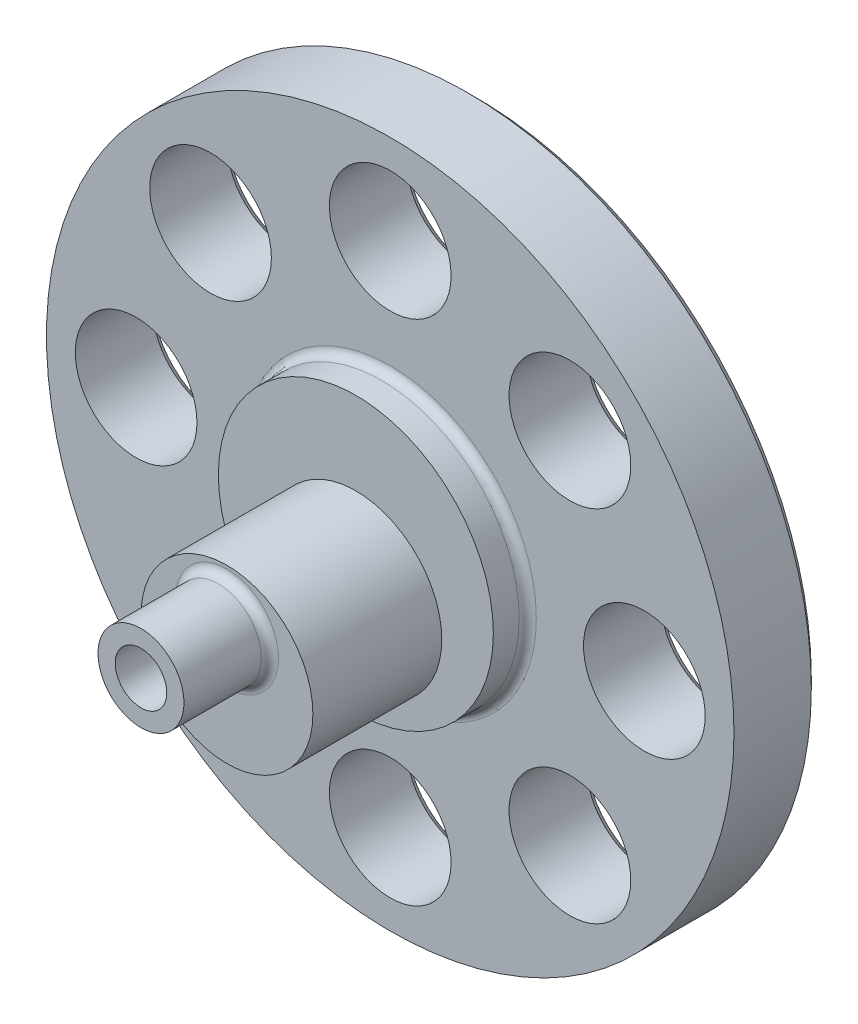
SolidWorks part; units mm, degrees
material "ABS PC"
ref_plane "Front Plane" through (0, 0, 0) normal (0, 0, 1) x (1, 0, 0)
ref_plane "Top Plane" through (0, 0, 0) normal (0, 1, 0) x (1, 0, 0)
ref_plane "Right Plane" through (0, 0, 0) normal (1, 0, 0) x (0, 0, -1)
sketch "Sketch1" plane through (0, 0, 0) normal (0, 0, 1) x (1, 0, 0)
  circle A2 centre (0, 0) radius 20
  circle A10 centre (-14.784, 0) radius 3.54
  circle A11 centre (-10.4538, -10.4538) radius 3.54
  circle A12 centre (0, -14.784) radius 3.54
  circle A13 centre (10.4538, -10.4538) radius 3.54
  circle A14 centre (14.784, 0) radius 3.54
  circle A15 centre (10.4538, 10.4538) radius 3.54
  circle A16 centre (0, 14.784) radius 3.54
  circle A17 centre (-10.4538, 10.4538) radius 3.54
  dimension "D1" = 7.08
  dimension "D2" = 40
extrude "Boss-Extrude1" add sketch "Sketch1" along normal blind 5
sketch "Sketch2" plane through (0, 0, 5) normal (0, 0, 1) x (1, 0, 0)
  circle A0 centre (0, 0) radius 8
  dimension "D1" = 16
extrude "Boss-Extrude2" add sketch "Sketch2" along normal blind 2
sketch "Sketch3" plane through (0, 0, 0) normal (0, 0, -1) x (-1, 0, 0)
  circle A0 centre (0, 0) radius 6.5
  dimension "D1" = 13
extrude "Cut-Extrude1" cut sketch "Sketch3" against normal blind 6
sketch "Sketch4" plane through (0, 0, 7) normal (0, 0, 1) x (1, 0, 0)
  circle A0 centre (0, -1.812) radius 5
  dimension "D2" = 10
  dimension "D1" = 1.812
extrude "Boss-Extrude3" add sketch "Sketch4" along normal blind 7.5
sketch "Sketch5" plane through (0, 0, 14.5) normal (0, 0, 1) x (1, 0, 0)
  circle A0 centre (0, 0) radius 2.5
  dimension "D1" = 5
extrude "Boss-Extrude4" add sketch "Sketch5" along normal blind 5
fillet "Fillet1" radius 0.5 1 edges at (8, 0, 5)
fillet "Fillet2" radius 0.5 1 edges at (2.5, 0, 14.5)
sketch "Sketch6" plane through (0, 0, 0) normal (0, 0, -1) x (-1, 0, 0)
  circle A0 centre (0, 0) radius 6.5
  circle A1 centre (0, 0) radius 3.5
  dimension "D1" = 7
extrude "Boss-Extrude5" [suppressed] add sketch "Sketch6" against normal blind 6
chamfer "Chamfer1" distance 0.5 angle 45 10 edges at (-6.9138, 10.4538, 0) (3.54, 14.784, 0) (13.9938, 10.4538, 0) (18.324, 0, 0) (13.9938, -10.4538, 0) (3.54, -14.784, 0) (-6.9138, -10.4538, 0) (-11.244, 0, 0) (20, 0, 0) (-6.5, 0, 0)
sketch "Sketch7" plane through (0, 0, 19.5) normal (0, 0, 1) x (1, 0, 0)
  circle A0 centre (0, 0) radius 1.5
  dimension "D1" = 3
extrude "Cut-Extrude2" cut sketch "Sketch7" against normal blind 15
